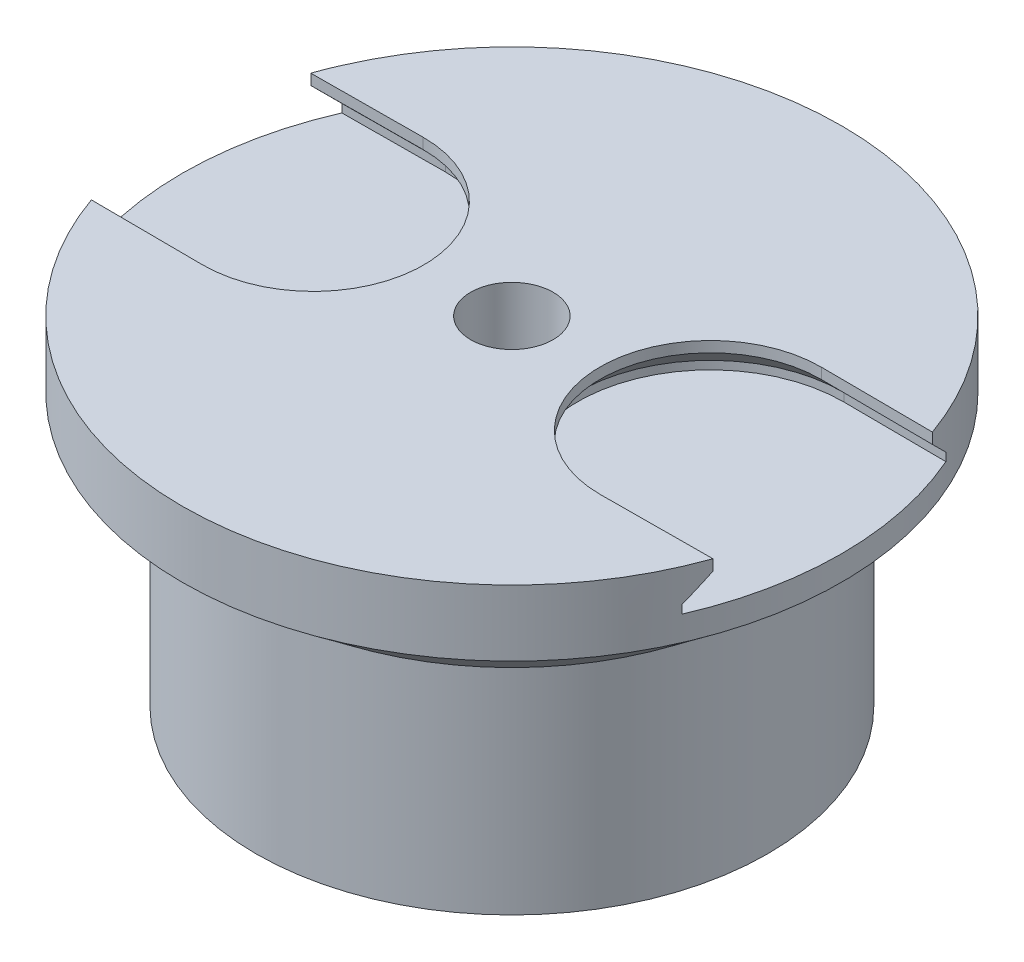
SolidWorks part; units mm, degrees
ref_plane "Front Plane" through (0, 0, 0) normal (0, 0, 1) x (1, 0, 0)
ref_plane "Top Plane" through (0, 0, 0) normal (0, 1, 0) x (1, 0, 0)
ref_plane "Right Plane" through (0, 0, 0) normal (1, 0, 0) x (0, 0, -1)
sketch "Sketch1" plane through (0, 0, 0) normal (0, 1, 0) x (1, 0, 0)
  circle A0 centre (0, 0) radius 31.06
  circle A1 centre (0, 0) radius 5
  dimension "D1" = 62.12
  dimension "D2" = 10
extrude "Boss-Extrude1" add sketch "Sketch1" along normal blind 35
sketch "Sketch18" plane through (0, 0, 0) normal (0, -1, 0) x (1, 0, 0)
  circle A0 centre (0, 0) radius 7.5
  circle A1 centre (0, 0) radius 28.66
  circle A2 centre (0, 0) radius 31.06 construction
  circle A3 centre (0, 0) radius 5 construction
  dimension "D1" = 2.4
  dimension "D2" = 2.5
extrude "Cut-Extrude12" cut sketch "Sketch18" against normal blind 13
sketch "Sketch19" plane through (0, 0, 0) normal (0, -1, 0) x (1, 0, 0)
  circle A0 centre (0, 0) radius 7.5 construction
  circle A1 centre (0, 0) radius 7.5
curve "Helix/Spiral1" pitch 12 height 12 radius 7.5 centre (0, 0, 0) axis (0, 1, 0) start towards (0, 0, -1)
sketch "Sketch20" plane through (0, 0, 0) normal (1, 0, 0) x (0, 0, -1)
  line L1 (-7.5, 0) -> (7.5, 0) construction
  line L2 (7.5, -0.6294) -> (7.5, 0.6294)
  line L4 (7.5, 0.6294) -> (8.5, 0.3457)
  line L5 (8.5, 0.3457) -> (8.5, -0.3956)
  line L6 (8.5, -0.3956) -> (7.5, -0.6294)
  line L7 (8, -0.5125) -> (8, 0.4875)
  line L8 (-7.5, 0) -> (7.5, 0)
  dimension "D1" = 1
  dimension "D2" = 29
  dimension "D3" = 1
sweep "Sweep2" add profiles "Sketch20" path "Helix/Spiral1"
pattern_circular "CirPattern8" count 4 over 360 about axis through (0, 0, 0) along (0, -1, 0) of "Sweep2"
sketch "Sketch24" plane through (0, 0, 0) normal (0, 0, 1) x (1, 0, 0)
  line L1 (-31.06, 0) -> (31.06, 0) construction
  line L2 (-31.06, 0) -> (-28.66, 0)
  line L3 (-31.06, 0) -> (-28.66, 2.4)
  line L5 (-28.66, 0) -> (-28.66, 2.4)
  line L6 (28.66, 0) -> (31.06, 0)
  dimension "D1" = 45
ref_axis "Axis1" through (0, 35, 0) along (0, -1, 0)
revolve "Cut-Revolve1" cut sketch "Sketch24" angle 360 about axis through (0, 35, 0) along (0, -1, 0)
sketch "Sketch25" plane through (0, 35, 0) normal (0, 1, 0) x (1, 0, 0)
sketch "Sketch28" plane through (0, 13, 0) normal (0, -1, 0) x (1, 0, 0)
  circle A0 centre (0, 0) radius 7.5 construction
  circle A1 centre (0, 0) radius 28.66
  circle A2 centre (0, 0) radius 28.66
  circle A3 centre (0, 0) radius 7.5
  dimension "D1" = 0
extrude "Cut-Extrude14" cut sketch "Sketch28" against normal blind 17 draft 32
sketch "Sketch30" plane through (0, 35, 0) normal (0, 1, 0) x (1, 0, 0)
  circle A0 centre (0, 0) radius 5 construction
  circle A2 centre (0, 0) radius 40
  circle A3 centre (0, 0) radius 5
  dimension "D1" = 80
extrude "Boss-Extrude2" add sketch "Sketch30" along normal blind 8
sketch "Sketch31" plane through (0, 43, 0) normal (0, 1, 0) x (1, 0, 0)
  line L0 (40, 0) -> (-40, 0)
  line L1 (40, 13.3) -> (40, -13.3)
  line L2 (40, -13.3) -> (24.1845, -13.3997)
  line L3 (40, 13.3) -> (16.7999, 13.4463)
  line L4 (0, -40) -> (0, 40)
  line L5 (-40, 13.3) -> (-16.7999, 13.4463)
  line L6 (-40, -13.3) -> (-24.1845, -13.3997)
  line L7 (-40, 13.3) -> (-40, -13.3)
  circle A0 centre (0, 0) radius 40 construction
  circle A1 centre (24.1, 0) radius 13.4
  circle A2 centre (-24.1, 0) radius 13.4
  circle M2 centre (0, 0) radius 40
  dimension "D1" = 26.8
  dimension "D2" = 26.6
  dimension "D3" = 15.9
extrude "Cut-Extrude16" cut sketch "Sketch31" against normal blind 1 from offset 4 contours A2 L0 | A2 L0 | L0 A2 L5 M2 | L6 A2 L0 M2 | A1 L0 | L0 A1 | A1 L2 L0 M2 | A1 L0 L3 M2 | A1 region at (36.0401, 43, 8.4076) region at (36.0401, 43, -8.4076) region at (24.1, 43, 5.6871) region at (24.1, 43, -5.6871) region at (-36.0401, 43, -8.4076) region at (-36.0401, 43, 8.4076) region at (-24.1, 43, 5.6871) region at (-24.1, 43, -5.6871) offset against normal yes
sketch "Sketch32" plane through (0, 43, 0) normal (0, 1, 0) x (1, 0, 0)
  line L0 (37.7191, 13.3144) -> (37.7191, -13.3144)
  line L1 (0, -40) -> (0, 40) construction
  line L2 (37.7191, 13.3144) -> (24.1845, 13.3997)
  line L3 (24.1845, -13.3997) -> (37.7191, -13.3144)
  line L4 (37.7191, 13.3144) -> (24.1845, 13.3997)
  line L5 (24.1845, -13.3997) -> (37.7191, -13.3144)
  line L6 (-24.1845, 13.3997) -> (-37.7191, 13.3144)
  line L7 (-37.7191, -13.3144) -> (-24.1845, -13.3997)
  line L8 (0, -40) -> (0, 40)
  line L9 (-24.1, -12) -> (-38.1576, -12)
  line L10 (31.06, 0) -> (24.1, 0)
  line L11 (-24.1, 12) -> (-38.1576, 12)
  line L12 (-31.06, 0) -> (-24.1, 0)
  line L13 (-24.1845, -13.3997) -> (-37.7191, -13.3144)
  line L14 (24.1, 12) -> (38.1576, 12)
  line L15 (24.1, -12) -> (38.1576, -12)
  line L16 (-37.7191, 13.3144) -> (-24.1845, 13.3997)
  line L17 (-37.7191, 13.3144) -> (-37.7191, -13.3144)
  circle A0 centre (24.1, 0) radius 12
  arc A1 (-24.1845, 13.3997) -> (-24.1845, -13.3997) centre (-24.1, 0) cw
  arc A2 (24.1845, 13.3997) -> (24.1845, -13.3997) centre (24.1, 0) ccw
  arc A3 (37.7191, -13.3144) -> (37.7191, 13.3144) centre (0, 0) ccw
  arc A4 (24.1845, 13.3997) -> (24.1845, -13.3997) centre (24.1, 0) ccw
  arc A5 (-37.7191, -13.3144) -> (37.7191, 13.3144) centre (0, 0) ccw
  arc A6 (-24.1845, -13.3997) -> (-24.1845, 13.3997) centre (-24.1, 0) ccw
  arc A7 (-37.7191, 13.3144) -> (-37.7191, -13.3144) centre (0, 0) ccw
  circle A8 centre (-24.1, 0) radius 12
  arc A9 (37.7191, 13.3144) -> (-37.7191, -13.3144) centre (0, 0) ccw
  circle M9 centre (0, 0) radius 40
  dimension "D4" = 24
  dimension "D1" = 0
  dimension "D2" = 0
extrude "Cut-Extrude17" cut sketch "Sketch32" against normal up to next contours A8 | L9 A8 L11 L17 | L17 L11 L9 M9 | A0 | A0 L15 L0 L14 | L0 L15 L14 M9 region at (38.6449, 43, 0) region at (37.4431, 43, 0) region at (32.3453, 43, -8.2453) region at (-38.6449, 43, 0) region at (-30.9095, 43, -11.7241) region at (-15.8547, 43, -8.2453)
ref_plane "Plane2" through (40, 0, 0) normal (1, 0, 0) x (0, 0, -1)
sketch "Sketch33" plane through (0, 38, 0) normal (0, 1, 0) x (1, 0, 0)
  line L0 (0, -40) -> (0, 40) construction
  line L1 (0, -40) -> (0, 40)
  line L2 (24.1845, -13.3997) -> (37.7191, -13.3144)
  line L3 (37.7191, 13.3144) -> (24.1845, 13.3997)
  line L4 (24.1845, -13.3997) -> (40, -13.3)
  line L5 (40, 13.3) -> (24.1845, 13.3997)
  line L6 (40, -40) -> (40, 40)
  line L7 (-40, -40) -> (-40, 40)
  line L8 (-40, 13.3) -> (-24.1845, 13.3997)
  line L9 (-24.1845, -13.3997) -> (-40, -13.3)
  arc A0 (-37.7191, -13.3144) -> (-37.7191, 13.3144) centre (0, 0) cw
  arc A1 (-24.1845, 13.3997) -> (-24.1845, -13.3997) centre (-24.1, 0) cw
  arc A2 (24.1845, 13.3997) -> (24.1845, -13.3997) centre (24.1, 0) ccw
  arc A3 (37.7191, -13.3144) -> (37.7191, 13.3144) centre (0, 0) ccw
  arc A4 (24.1845, 13.3997) -> (24.1845, -13.3997) centre (24.1, 0) ccw
  arc A5 (37.7191, -13.3144) -> (37.7191, 13.3144) centre (0, 0) ccw
  dimension "D1" = 0
  dimension "D2" = 40
sketch "Sketch34" plane through (40, 0, 0) normal (1, 0, 0) x (0, 0, -1)
  line L0 (-40, 38) -> (40, 38) construction
  line L1 (-40, 38) -> (40, 38)
  line L2 (-13.3997, 38) -> (-13.3, 38) construction
  line L3 (-13.3997, 38) -> (-13.3, 38)
  line L4 (-13.3, 38) -> (-16, 38)
  line L5 (-16, 38) -> (-16, 39)
  line L6 (-16, 39) -> (-13.3, 41.7)
  line L7 (-13.3, 41.7) -> (-13.3, 38)
  line L8 (-13.3144, 38) -> (-13.3144, 39) construction
  dimension "D1" = 2.7
  dimension "D2" = 45
sweep "Cut-Sweep1" cut profiles "Sketch34" path "Sketch33"
sketch "Sketch35" plane through (0, 43, 0) normal (0, 1, 0) x (1, 0, 0)
  line L4 (-38.1576, 12) -> (-24.1, 12)
  line L5 (-38.1576, 12) -> (-24.1, 12)
  line L6 (38.1576, -12) -> (24.1, -12)
  line L7 (24.1, 12) -> (38.1576, 12)
  line L8 (-24.1, -12) -> (-38.1576, -12)
  line L9 (-24.1, -12) -> (-38.1576, -12)
  line L10 (38.1576, -12) -> (24.1, -12)
  line L11 (24.1, 12) -> (38.1576, 12)
  line L12 (24.1, 12) -> (38.1576, 12)
  line L13 (38.1576, -12) -> (24.1, -12)
  line L14 (24.1845, -13.3997) -> (37.7191, -13.3144)
  line L15 (37.7191, 13.3144) -> (24.1845, 13.3997)
  line L16 (24.1, 12) -> (38.1576, 12)
  line L17 (38.1576, -12) -> (24.1, -12)
  line L18 (24.1845, -13.3997) -> (37.7191, -13.3144)
  line L19 (37.7191, 13.3144) -> (24.1845, 13.3997)
  arc A4 (-24.1, -12) -> (-24.1, 12) centre (-24.1, 0) ccw
  arc A5 (-38.1576, -12) -> (38.1576, -12) centre (0, 0) ccw
  arc A6 (24.1, 12) -> (24.1, -12) centre (24.1, 0) ccw
  arc A7 (38.1576, 12) -> (-38.1576, 12) centre (0, 0) ccw
  arc A8 (-24.1, -12) -> (-24.1, 12) centre (-24.1, 0) ccw
  arc A9 (-38.1576, -12) -> (38.1576, -12) centre (0, 0) ccw
  arc A10 (24.1, 12) -> (24.1, -12) centre (24.1, 0) ccw
  arc A11 (38.1576, 12) -> (-38.1576, 12) centre (0, 0) ccw
  arc A12 (24.1, 12) -> (24.1, -12) centre (24.1, 0) ccw
  arc A13 (37.7191, -13.3144) -> (38.1576, -12) centre (0, 0) ccw
  arc A14 (24.1845, 13.3997) -> (24.1845, -13.3997) centre (24.1, 0) ccw
  arc A15 (38.1576, 12) -> (37.7191, 13.3144) centre (0, 0) ccw
  arc A16 (24.1, 12) -> (24.1, -12) centre (24.1, 0) ccw
  arc A17 (37.7191, -13.3144) -> (38.1576, -12) centre (0, 0) ccw
  arc A18 (24.1845, 13.3997) -> (24.1845, -13.3997) centre (24.1, 0) ccw
  arc A19 (38.1576, 12) -> (37.7191, 13.3144) centre (0, 0) ccw
  arc M12 (-38.1576, -12) -> (38.1576, -12) centre (0, 0) ccw
  line M13 (38.1576, -12) -> (24.1, -12)
  arc M14 (24.1, -12) -> (24.1, 12) centre (24.1, 0) cw
  line M15 (24.1, 12) -> (38.1576, 12)
  arc M16 (38.1576, 12) -> (-38.1576, 12) centre (0, 0) ccw
  dimension "D1" = 0
  dimension "D2" = 0
extrude "Cut-Extrude19" cut sketch "Sketch35" against normal up to next contours L19 A18 L18 M12 M13 M14 M15 M16 region at (37.58, 43, -12.5377)
ref_plane "Plane3" through (-40, 0, 0) normal (-1, 0, 0) x (0, 0, 1)
sketch "Sketch37" plane through (-40, 0, 0) normal (-1, 0, 0) x (0, 0, 1)
  line L0 (40, 38) -> (-40, 38) construction
  line L1 (40, 38) -> (-40, 38)
  line L2 (-13.3, 38) -> (-13.3997, 38) construction
  line L3 (-13.3, 38) -> (-13.3997, 38)
  line L4 (-13.3, 38) -> (-16, 38)
  line L5 (-16, 38) -> (-16, 39)
  line L6 (-16, 39) -> (-13.3, 41.7)
  line L7 (-13.3, 41.7) -> (-13.3, 38)
  line L8 (-13.3144, 38) -> (-13.3144, 39) construction
  dimension "D1" = 45
  dimension "D2" = 2.7
sweep "Cut-Sweep2" cut profiles "Sketch37" path "Sketch33<3>"
sketch "Sketch33<3>" plane through (0, 38, 0) normal (0, 1, 0) x (1, 0, 0) same geometry as "Sketch33"
sketch "Sketch38" plane through (0, 43, 0) normal (0, 1, 0) x (1, 0, 0)
  line L4 (24.1845, 13.3997) -> (37.7191, 13.3144)
  line L5 (24.1845, 13.3997) -> (37.7191, 13.3144)
  line L6 (-38.1576, 12) -> (-24.1, 12)
  line L7 (-24.1, -12) -> (-38.1576, -12)
  line L8 (37.7191, -13.3144) -> (24.1845, -13.3997)
  line L9 (37.7191, -13.3144) -> (24.1845, -13.3997)
  line L10 (-38.1576, 12) -> (-24.1, 12)
  line L11 (-24.1, -12) -> (-38.1576, -12)
  line L12 (-38.1576, 12) -> (-24.1, 12)
  line L13 (-24.1845, 13.3997) -> (-37.7191, 13.3144)
  line L14 (-37.7191, -13.3144) -> (-24.1845, -13.3997)
  line L15 (-24.1, -12) -> (-38.1576, -12)
  line L16 (-38.1576, 12) -> (-24.1, 12)
  line L17 (-24.1845, 13.3997) -> (-37.7191, 13.3144)
  line L18 (-37.7191, -13.3144) -> (-24.1845, -13.3997)
  line L19 (-24.1, -12) -> (-38.1576, -12)
  arc A4 (24.1845, 13.3997) -> (24.1845, -13.3997) centre (24.1, 0) ccw
  arc A5 (37.7191, 13.3144) -> (-38.1576, 12) centre (0, 0) ccw
  arc A6 (-24.1, -12) -> (-24.1, 12) centre (-24.1, 0) ccw
  arc A7 (-38.1576, -12) -> (37.7191, -13.3144) centre (0, 0) ccw
  arc A8 (24.1845, 13.3997) -> (24.1845, -13.3997) centre (24.1, 0) ccw
  arc A9 (37.7191, 13.3144) -> (-38.1576, 12) centre (0, 0) ccw
  arc A10 (-24.1, -12) -> (-24.1, 12) centre (-24.1, 0) ccw
  arc A11 (-38.1576, -12) -> (37.7191, -13.3144) centre (0, 0) ccw
  arc A12 (-24.1, -12) -> (-24.1, 12) centre (-24.1, 0) ccw
  arc A13 (-37.7191, 13.3144) -> (-38.1576, 12) centre (0, 0) ccw
  arc A14 (-24.1845, -13.3997) -> (-24.1845, 13.3997) centre (-24.1, 0) ccw
  arc A15 (-38.1576, -12) -> (-37.7191, -13.3144) centre (0, 0) ccw
  arc A16 (-24.1, -12) -> (-24.1, 12) centre (-24.1, 0) ccw
  arc A17 (-37.7191, 13.3144) -> (-38.1576, 12) centre (0, 0) ccw
  arc A18 (-24.1845, -13.3997) -> (-24.1845, 13.3997) centre (-24.1, 0) ccw
  arc A19 (-38.1576, -12) -> (-37.7191, -13.3144) centre (0, 0) ccw
  arc M12 (37.7191, 13.3144) -> (-38.1576, 12) centre (0, 0) ccw
  line M13 (-38.1576, 12) -> (-24.1, 12)
  arc M14 (-24.1, 12) -> (-24.1, -12) centre (-24.1, 0) cw
  line M15 (-24.1, -12) -> (-38.1576, -12)
  arc M16 (-38.1576, -12) -> (37.7191, -13.3144) centre (0, 0) ccw
  dimension "D1" = 0
  dimension "D2" = 0
extrude "Cut-Extrude20" cut sketch "Sketch38" against normal up to next contours L18 A18 L17 M12 M13 M14 M15 M16 region at (-30.9494, 43, -12.9734)
ref_plane "Plane4" through (0, 28, 0) normal (0, 1, 0) x (1, 0, 0)
sketch "Sketch39" plane through (0, 28, 0) normal (0, 1, 0) x (1, 0, 0)
  circle A1 centre (0, 0) radius 31.06 construction
  circle A2 centre (0, 0) radius 31.06
sketch "Sketch40" plane through (0, 0, 0) normal (0, 0, 1) x (1, 0, 0)
  line L0 (-40, 35) -> (40, 35) construction
  line L1 (-40, 35) -> (40, 35)
  line L2 (31.06, 28) -> (-31.06, 28) construction
  line L3 (31.06, 28) -> (-31.06, 28)
  line L4 (-31.06, 28) -> (-40, 35)
  line L5 (-31.06, 28) -> (-31.06, 35)
  line L6 (-31.06, 35) -> (-31.06, 0) construction
  line L7 (-31.06, 35) -> (-40, 35)
revolve "Revolve1" add sketch "Sketch40" angle 360 about axis through (0, 35, 0) along (0, -1, 0) region at (-34.04, 32.6667, 0)
sketch "Sketch41" plane through (0, 0, 0) normal (0, -1, 0) x (1, 0, 0)
  circle A0 centre (0, 0) radius 10
  dimension "D1" = 20
extrude "Cut-Extrude21" cut sketch "Sketch41" along normal blind 10
sketch "Sketch42" plane through (0, 0, 0) normal (0, -1, 0) x (1, 0, 0)
  circle A1 centre (0, 0) radius 31.06
extrude "Cut-Extrude22" cut sketch "Sketch42" against normal blind 2
